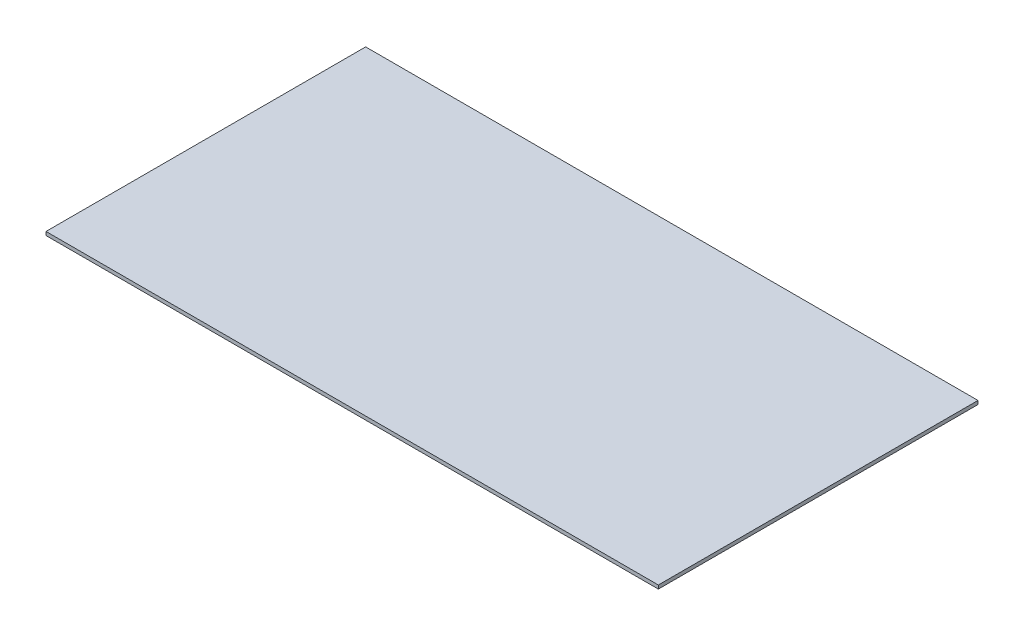
SolidWorks part; units mm, degrees
material "5052-H34"
ref_plane "Front Plane" through (0, 0, 0) normal (0, 0, 1) x (1, 0, 0)
ref_plane "Top Plane" through (0, 0, 0) normal (0, 1, 0) x (1, 0, 0)
ref_plane "Right Plane" through (0, 0, 0) normal (1, 0, 0) x (0, 0, -1)
sketch "Sketch1" plane through (0, 0, 0) normal (0, 0, 1) x (1, 0, 0)
  line L0 (-580.595, 2.8542) -> (-36.865, 2.8542)
  line L1 (-36.865, 2.8542) -> (-36.865, -0.3208)
  line L3 (-36.865, -0.3208) -> (-580.595, -0.3208)
  line L6 (-580.595, 2.8542) -> (-580.595, -0.3208)
  point P2 (-580.595, 2.8542)
  dimension "D1" = 3.175
  dimension "D2" = 543.73
  dimension "D3" = 36.865
  dimension "D4" = 2.8542
extrude "Boss-Extrude1" add sketch "Sketch1" along normal blind 283.825
sketch "GasketGroove" plane through (0, -0.3208, 0) normal (0, -1, 0) x (1, 0, 0)
  line L0 (-577.595, 279.825) -> (-577.595, 4)
  line L1 (-576.595, 3) -> (-40.865, 3)
  line L2 (-39.865, 4) -> (-39.865, 279.825)
  line L3 (-40.865, 280.825) -> (-576.595, 280.825)
  line L4 (-579.595, 282.825) -> (-579.595, 1) construction
  line L5 (-577.595, 282.825) -> (-577.595, 1) construction
  line L6 (-37.865, 280.825) -> (-579.595, 280.825) construction
  line L7 (-579.595, 3) -> (-37.865, 3) construction
  line L8 (-39.865, 1) -> (-39.865, 282.825) construction
  line L9 (-579.595, 1) -> (-37.865, 1) construction
  line L10 (-37.865, 282.825) -> (-579.595, 282.825) construction
  line L11 (-37.865, 1) -> (-37.865, 282.825) construction
  line L14 (-37.865, 1) -> (-37.865, 282.825)
  line L15 (-579.595, 1) -> (-37.865, 1)
  line L16 (-579.595, 282.825) -> (-579.595, 1)
  line L17 (-37.865, 282.825) -> (-579.595, 282.825)
  line L18 (-37.865, 2) -> (-37.865, 281.825)
  line L19 (-578.595, 1) -> (-38.865, 1)
  line L20 (-579.595, 281.825) -> (-579.595, 2)
  line L21 (-38.865, 282.825) -> (-578.595, 282.825)
  arc A0 (-579.595, 2) -> (-578.595, 1) centre (-578.595, 2) ccw
  arc A1 (-579.595, 281.825) -> (-578.595, 282.825) centre (-578.595, 281.825) cw
  arc A2 (-37.865, 281.825) -> (-38.865, 282.825) centre (-38.865, 281.825) ccw
  arc A3 (-38.865, 1) -> (-37.865, 2) centre (-38.865, 2) ccw
  arc A4 (-40.865, 3) -> (-39.865, 4) centre (-40.865, 4) ccw
  arc A5 (-576.595, 3) -> (-577.595, 4) centre (-576.595, 4) cw
  arc A6 (-576.595, 280.825) -> (-577.595, 279.825) centre (-576.595, 279.825) ccw
  arc A7 (-39.865, 279.825) -> (-40.865, 280.825) centre (-40.865, 279.825) ccw
  dimension "D6" = 1
  dimension "D7" = 1
  dimension "D8" = 1
  dimension "D9" = 1
  dimension "D10" = 1
  dimension "D11" = 1
  dimension "D12" = 1
  dimension "D13" = 1
  dimension "D1" = 1
  dimension "D2" = 2
  dimension "D3" = 2
  dimension "D4" = 2
  dimension "D5" = 2
extrude "Cut-Extrude1" cut sketch "GasketGroove" against normal blind 1.3
